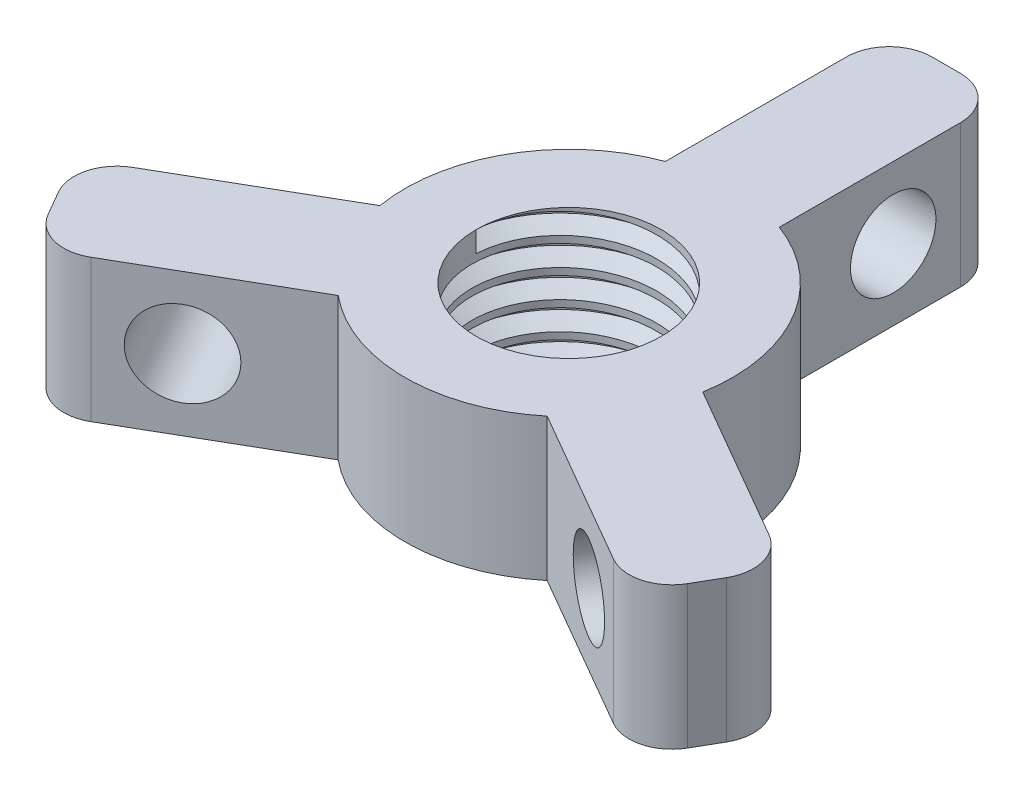
SolidWorks part; units mm, degrees
material "ASTM A36 Acero"
ref_plane "Front" through (0, 0, 0) normal (0, 0, 1) x (1, 0, 0)
ref_plane "Top" through (0, 0, 0) normal (0, 1, 0) x (1, 0, 0)
ref_plane "Right" through (0, 0, 0) normal (1, 0, 0) x (0, 0, -1)
sketch "Croquis1" plane through (0, 0, 0) normal (0, 1, 0) x (1, 0, 0)
  circle A0 centre (0, 0) radius 6.5
  circle A1 centre (0, 0) radius 11.5
  dimension "D1" = 13
  dimension "D2" = 5
extrude "Saliente-Extruir1" add sketch "Croquis1" along normal mid plane 10
thread "Rosca1" pitch 1.9538 method cut profile "Perfil de rosca1" start angle 0, offset 0, length 10, pitch 1.9538, diameter 13
ref_plane "Plano1" through (-6.5, 5, 0) normal (0, 0, 1) x (-1, 0, 0)
sketch "Perfil de rosca1" plane through (-6.5, 5, 0) normal (0, 0, 1) x (-1, 0, 0)
  line L0 (0, 0) -> (0, 1.9538) construction
  line L1 (0, 0) -> (1.0576, 0.6106)
  line L2 (1.0576, 0.6106) -> (1.0576, 0.8548)
  line L3 (1.0576, 0.8548) -> (0, 1.4654)
  line L4 (1.0576, 0.7327) -> (0, 0.7327) construction
  line L11 (0, 0) -> (0, 1.4654)
  point P2 (0, 0)
  dimension "Pitch" = 1.9538
  dimension "Profile_Angle" = 60
  dimension "Profile_Land" = 0.2442
  dimension "Profile_Height" = 1.0576
sketch "Croquis6" plane through (0, 0, 0) normal (0, 1, 0) x (1, 0, 0)
  line L0 (-4, 10.7819) -> (-4, 23.5)
  line L1 (-1, 26.5) -> (1, 26.5)
  line L2 (4, 23.5) -> (4, 10.7819)
  line L3 (0, 0) -> (0, 31.8583) construction
  line L4 (-24.5686, 11.5) -> (24.5686, 11.5) construction
  circle A0 centre (0, 0) radius 11.5 construction
  arc A1 (4, 10.7819) -> (-4, 10.7819) centre (0, 0) ccw
  arc A2 (1, 26.5) -> (4, 23.5) centre (1, 23.5) cw
  arc A3 (-4, 23.5) -> (-1, 26.5) centre (-1, 23.5) cw
  point P8 (0, 26.5)
  point P13 (0, 11.5)
  point P16 (4, 26.5)
  point P19 (-4, 26.5)
  dimension "D3" = 3
  dimension "D1" = 8
  dimension "D2" = 15
extrude "Saliente-Extruir2" add sketch "Croquis6" along direction (0, 1, 0) on the side of the normal mid plane 10
sketch "Croquis7" plane through (-4, 0, 0) normal (-1, 0, 0) x (0, 0, 1)
  line L0 (-23.5, 0) -> (-10.7819, 0) construction
  line L1 (-23.5, 5) -> (-23.5, -5) construction
  line L2 (-10.7819, 5) -> (-10.7819, -5) construction
  circle A0 centre (-18.7819, 0) radius 3
  dimension "D2" = 6
  dimension "D1" = 8
extrude "Cortar-Extruir1" cut sketch "Croquis7" against normal up to next
pattern_circular "MatrizC1" count 3 over 360 about axis through (0, 5, 0) along (0, 1, 0) of "Cortar-Extruir1", "Saliente-Extruir2"
